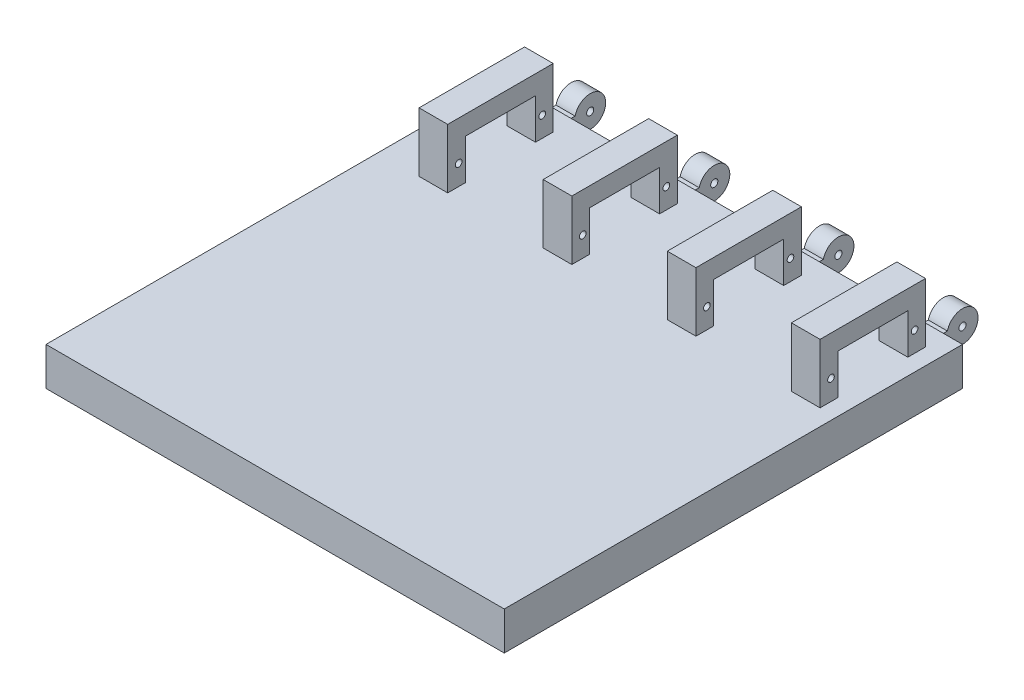
SolidWorks part; units mm, degrees
material "ABS"
ref_plane "Front Plane" through (0, 0, 0) normal (0, 0, 1) x (1, 0, 0)
ref_plane "Top Plane" through (0, 0, 0) normal (0, 1, 0) x (1, 0, 0)
ref_plane "Right Plane" through (0, 0, 0) normal (1, 0, 0) x (0, 0, -1)
sketch "Sketch2" plane through (0, 0, 0) normal (0, 1, 0) x (1, 0, 0)
  line L0 (0, 0) -> (-152.4, 0)
  line L1 (-152.4, 0) -> (-152.4, -152.4)
  line L2 (-152.4, -152.4) -> (0, -152.4)
  line L3 (0, -152.4) -> (0, 0)
  dimension "D1" = 152.4
  dimension "D2" = 152.4
extrude "Boss-Extrude2" add sketch "Sketch2" along normal blind 12.7
ref_plane "Plane2" through (-14.9327, 0, 0) normal (1, 0, 0) x (0, 0, -1)
ref_plane "Plane1" through (-12.7, 0, 0) normal (1, 0, 0) x (0, 0, -1)
sketch "Sketch3" plane through (-12.7, 0, 0) normal (1, 0, 0) x (0, 0, -1)
  line L0 (0, 6.35) -> (0, 0)
  line L2 (0, 12.7) -> (0, 0) construction
  line L3 (0, 0) -> (12.7, 0)
  line L4 (12.7, 0) -> (12.7, 6.35)
  line L5 (12.7, 6.35) -> (0, 6.35)
  circle A3 centre (12.7, 5.1562) radius 5.1562
  circle A5 centre (12.7, 5.1562) radius 1.1913
  dimension "D3" = 10.3124
  dimension "D2" = 0
  dimension "D1" = 6.35
extrude "Boss-Extrude3" add sketch "Sketch3" against normal blind 6.35 contours A5 L4 L3 A3 | A5 L4 A3 L3 | A3 L5 L0 L3 region at (-12.7, 2.9629, -4.2993) region at (-12.7, 5.9308, -13.8075) region at (-12.7, 3.4565, -10.2697)
sketch "Sketch4" plane through (-14.9327, 0, 0) normal (1, 0, 0) x (0, 0, -1)
  line L0 (-6.891, 12.7) -> (-6.891, 32.4402)
  line L1 (-152.4, 12.7) -> (0, 12.7) construction
  line L2 (-6.891, 32.4402) -> (-41.9716, 32.4402)
  line L3 (-41.9716, 32.4402) -> (-41.9716, 12.7)
  line L4 (-41.9716, 12.7) -> (-36.0778, 12.7)
  line L5 (-36.0778, 12.7) -> (-36.0778, 26.0902)
  line L6 (-36.0778, 26.0902) -> (-12.7848, 26.0902)
  line L7 (-12.7848, 26.0902) -> (-12.7848, 12.7)
  line L8 (-12.7848, 12.7) -> (-6.891, 12.7)
  circle A0 centre (-10.5324, 19.3964) radius 1.0998
  circle A2 centre (-38.3327, 19.3952) radius 1.0998
  point P30 (-39.0247, 12.7)
  dimension "D7" = 6.6964
  dimension "D1" = 23.2931
  dimension "D2" = 5.8938
  dimension "D3" = 5.8938
  dimension "D4" = 6.35
  dimension "D5" = 6.891
  dimension "D6" = 13.3902
  dimension "D8" = 3.6414
  dimension "D9" = 27.8003
extrude "Boss-Extrude4" add sketch "Sketch4" along normal blind 9.525
pattern_linear "LPattern1" count 4 spacing 41.275 along (-1, 0, 0) of "Boss-Extrude3", "Boss-Extrude4"
